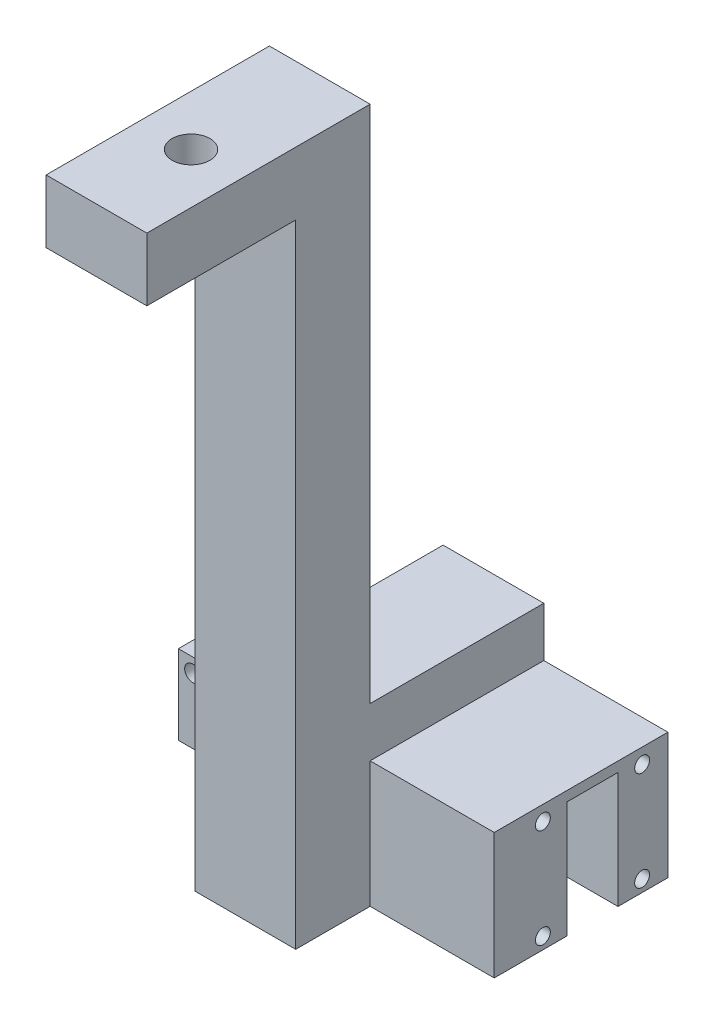
SolidWorks part; units mm, degrees
ref_plane "Front Plane" through (0, 0, 0) normal (0, 0, 1) x (1, 0, 0)
ref_plane "Top Plane" through (0, 0, 0) normal (0, 1, 0) x (1, 0, 0)
ref_plane "Right Plane" through (0, 0, 0) normal (1, 0, 0) x (0, 0, -1)
sketch "Sketch1" plane through (0, 0, 0) normal (1, 0, 0) x (0, 0, -1)
  line L0 (0, 25.4) -> (5, 25.4)
  line L3 (0, 25.4) -> (-30, 25.4)
  line L4 (-30, 0) -> (-30, 25.4)
  line L5 (-30, 0) -> (-45, 0)
  line L6 (-30, 0) -> (-30, 127.3)
  line L7 (-30, 127.3) -> (-45, 127.3)
  line L8 (-45, 0) -> (-45, 127.3)
  line L9 (-30, 127.3) -> (-75, 127.3)
  line L10 (-30, 127.3) -> (-30, 140)
  line L11 (-30, 140) -> (-75, 140)
  line L12 (-75, 127.3) -> (-75, 140)
  line L15 (-30, 0) -> (0, 0)
  line L16 (0, 25.4) -> (0, 0)
  line L17 (-15.35, 0) -> (-5.05, 0)
  line L18 (-15.35, 0) -> (-15.35, 15)
  line L19 (-15.35, 15) -> (-5.05, 15)
  line L20 (-5.05, 0) -> (-5.05, 15)
  line L21 (-15.35, 23.4) -> (-5.05, 23.4)
  line L22 (-15.35, 23.4) -> (-15.35, 18.4)
  line L23 (-15.35, 18.4) -> (-5.05, 18.4)
  line L24 (-5.05, 23.4) -> (-5.05, 18.4)
  line L25 (5, 25.4) -> (5, 0)
  line L26 (5, 0) -> (0, 0)
  line L27 (-5.05, 18.4) -> (-5.05, 15)
  line L28 (-15.35, 18.4) -> (-15.35, 15)
  line L29 (5, 25.4) -> (5, 35.4)
  line L30 (5, 35.4) -> (-30, 35.4)
  circle A0 centre (-0.195, 22.4) radius 1.5
  circle A1 centre (-20.195, 22.4) radius 1.5
  circle A2 centre (-20.195, 2.4) radius 1.5
  circle A3 centre (-0.195, 2.4) radius 1.5
  point P31 (-10.2, 23.4)
  dimension "D2" = 140
  dimension "D16" = 3
  dimension "D17" = 10.005
  dimension "D3" = 10.3
  dimension "D4" = 25.4
  dimension "D5" = 15
  dimension "D6" = 5.05
  dimension "D7" = 30
  dimension "D8" = 15
  dimension "D9" = 45
  dimension "D10" = 5
  dimension "D11" = 12.7
  dimension "D12" = 2
  dimension "D13" = 3.4
  dimension "D14" = 20
  dimension "D15" = 20
  dimension "D18" = 3
  dimension "D19" = 9.995
  dimension "D20" = 5
  dimension "D21" = 10
extrude "Boss-Extrude1" add sketch "Sketch1" along normal blind 5 contours L12 L9 L7 L10 L11 | L8 L5 L4 L6 L7 | L4 L3 | A3 L16 L26 L25 L0 A0 | L29 L30 L6 L3 L0 region at (0, 30.4, 12.5) region at (0, 13.1968, 17.4087) region at (0, 12.7146, -2.5951) region at (0, 63.65, 37.5) region at (0, 133.65, 52.5)
extrude "Boss-Extrude2" add sketch "Sketch1<4>" along normal blind 10.3 from surface contours L8 L5 L4 L6 L7 | L12 L9 L7 L10 L11 | L3 L4 | A3 L16 L26 L25 L0 A0 region at (0, 13.1968, 17.4087) region at (0, 12.7146, -2.5951) region at (0, 63.65, 37.5) region at (0, 133.65, 52.5) starting at face at (5, 2.4, -1.305)
sketch "Sketch1<4>" plane through (0, 0, 0) normal (1, 0, 0) x (0, 0, -1) same geometry as "Sketch1"
extrude "Boss-Extrude3" add sketch "Sketch1<5>" along normal blind 5 from surface contours L4 L3 | L8 L5 L4 L6 L7 | L12 L9 L7 L10 L11 | A3 L16 L26 L25 L0 A0 | L23 L28 L19 L27 | L29 L30 L6 L3 L0 region at (0, 30.4, 12.5) region at (0, 13.1968, 17.4087) region at (0, 12.7146, -2.5951) region at (0, 63.65, 37.5) region at (0, 133.65, 52.5) region at (0, 16.7, 10.2) starting at face at (15.3, 52.6833, 27.5667)
sketch "Sketch1<5>" plane through (0, 0, 0) normal (1, 0, 0) x (0, 0, -1) same geometry as "Sketch1"
sketch "Sketch2" plane through (0, 0, 0) normal (0, 0, 1) x (1, 0, 0)
  line L1 (48.3, 16) -> (20.3, 16)
  line L2 (48.3, 16) -> (48.3, 0)
  line L3 (48.3, 0) -> (20.3, 0)
  line L4 (20.3, 16) -> (20.3, 0)
  line L5 (15.3, 25.4) -> (5, 25.4) construction
  line L9 (20.3, 0) -> (20.3, 35.4) construction
  line L10 (20.3, 0) -> (0, 0) construction
  line L11 (10.15, 25.4) -> (10.15, 0) construction
  line L13 (0, 16) -> (0, 0)
  line L14 (-28, 0) -> (0, 0)
  line L15 (-28, 16) -> (-28, 0)
  line L16 (-28, 16) -> (0, 16)
  circle A0 centre (45.4, 13.15) radius 1.625
  circle A1 centre (23.2, 2.85) radius 1.625
  circle A2 centre (-2.9, 2.85) radius 1.625
  circle A3 centre (-25.1, 13.15) radius 1.625
  dimension "D1" = 3.25
  dimension "D2" = 28
  dimension "D3" = 16
  dimension "D4" = 10.3
  dimension "D5" = 22.2
  dimension "D6" = 2.9
  dimension "D7" = 2.85
extrude "Boss-Extrude4" add sketch "Sketch2" along normal blind 5 contours L16 L15 L14 L13 A2 A3 region at (-14, 8, 0)
extrude "Boss-Extrude5" add sketch "Sketch2<2>" along normal blind 5 from surface contours L16 L15 L14 L13 A2 A3 region at (-14, 8, 0) starting at face at (13.975, 14.2, 15.35)
sketch "Sketch2<2>" plane through (0, 0, 0) normal (0, 0, 1) x (1, 0, 0) same geometry as "Sketch2"
sketch "Sketch3" plane through (0, 0, 0) normal (0, 1, 0) x (1, 0, 0)
  line L0 (20.3, -75) -> (0, -75) construction
  line L1 (20.3, -75) -> (20.3, -45) construction
  line L2 (0, -45) -> (0, -75) construction
  circle A0 centre (10.15, -55.95) radius 3.81
  dimension "D1" = 7.62
  dimension "D2" = 19.05
  dimension "D3" = 10.15
  dimension "D4" = 10.15
extrude "Cut-Extrude1" cut sketch "Sketch3" along normal up to surface (140 mm away) from surface up to face at (10.15, 140, 52.5) starting at face at (10.15, 127.3, 60)
extrude "Boss-Extrude6" add sketch "Sketch1<6>" along normal blind 25 from surface contours A3 L16 A0 L3 L4 L15 L18 L19 L20 A2 A1 L21 L24 L23 L22 | A3 L16 L26 L25 L0 A0 region at (0, 13.1968, 17.4087) region at (0, 12.7146, -2.5951) starting at face at (20.3, 22.4, 21.695)
sketch "Sketch1<6>" plane through (0, 0, 0) normal (1, 0, 0) x (0, 0, -1) same geometry as "Sketch1"
extrude "Boss-Extrude7" add sketch "Sketch1<7>" against normal blind 5 from surface contours L23 L28 L19 L27 region at (0, 16.7, 10.2) starting at face at (15.3, 16.7, 10.2)
sketch "Sketch1<7>" plane through (0, 0, 0) normal (1, 0, 0) x (0, 0, -1) same geometry as "Sketch1"
extrude "Boss-Extrude8" add sketch "Sketch1<9>" along normal blind 20 contours L29 L30 L6 L3 L0 region at (0, 30.4, 12.5)
sketch "Sketch1<9>" plane through (0, 0, 0) normal (1, 0, 0) x (0, 0, -1) same geometry as "Sketch1"
equation "\"D6@Sketch2\"= (\"D2@Sketch2\"-\"D5@Sketch2\")/2"
equation "\"D7@Sketch2\"=(\"D3@Sketch2\"-\"D4@Sketch2\")/2"
